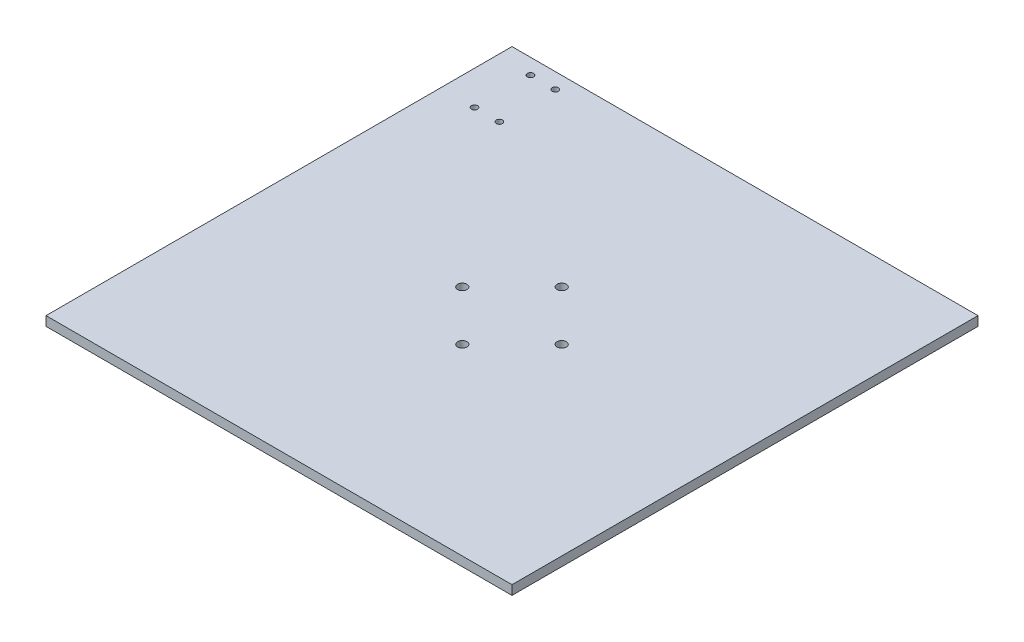
SolidWorks part; units mm, degrees
ref_plane "Front Plane" through (0, 0, 0) normal (0, 0, 1) x (1, 0, 0)
ref_plane "Top Plane" through (0, 0, 0) normal (0, 1, 0) x (1, 0, 0)
ref_plane "Right Plane" through (0, 0, 0) normal (1, 0, 0) x (0, 0, -1)
sketch "Sketch1" plane through (0, 0, 0) normal (0, 1, 0) x (1, 0, 0)
  line L1 (0, 0) -> (150, 0)
  line L2 (0, 0) -> (0, 150)
  line L3 (0, 150) -> (150, 150)
  line L4 (150, 0) -> (150, 150)
  dimension "D1" = 150
  dimension "D2" = 150
extrude "Boss-Extrude1" add sketch "Sketch1" along normal blind 3
sketch "Sketch2" plane through (0, 3, 0) normal (0, 1, 0) x (1, 0, 0)
  line L0 (150, 150) -> (0, 150) construction
  line L1 (0, 150) -> (0, 0) construction
  line L2 (75, 75) -> (75, 150) construction
  line L3 (75, 75) -> (210.7511, 75) construction
  line L4 (59, 75) -> (75, 75) construction
  line L5 (75, 75) -> (75, 91) construction
  line L6 (91, 75) -> (75, 75) construction
  line L7 (75, 59) -> (75, 75) construction
  circle A0 centre (75, 75) radius 3.5 construction
  circle A1 centre (75, 59) radius 1.5
  circle A2 centre (59, 75) radius 1.5
  circle A3 centre (75, 91) radius 1.5
  circle A4 centre (91, 75) radius 1.5
  circle A5 centre (18.93, 145) radius 1
  circle A6 centre (10.93, 145) radius 1
  circle A7 centre (18.93, 127) radius 1
  circle A8 centre (10.93, 127) radius 1
  point P4 (0, 0)
  point P22 (25.8681, -81.547)
  point P25 (25.8681, -81.547)
  point P29 (25.8681, -81.547)
  point P31 (25.8681, -81.547)
  point P32 (25.8681, -81.547)
  point P33 (25.8681, -81.547)
  point P36 (25.8681, -81.547)
  point P37 (25.8681, -81.547)
  dimension "D1" = 7
  dimension "D2" = 3
  dimension "D4" = 18
  dimension "D5" = 2
  dimension "D3" = 16
  dimension "D6" = 8
  dimension "D7" = 5
  dimension "D8" = 10.93
  dimension "D9" = 75
  dimension "D10" = 75
extrude "Cut-Extrude1" cut sketch "Sketch2" against normal blind 10
